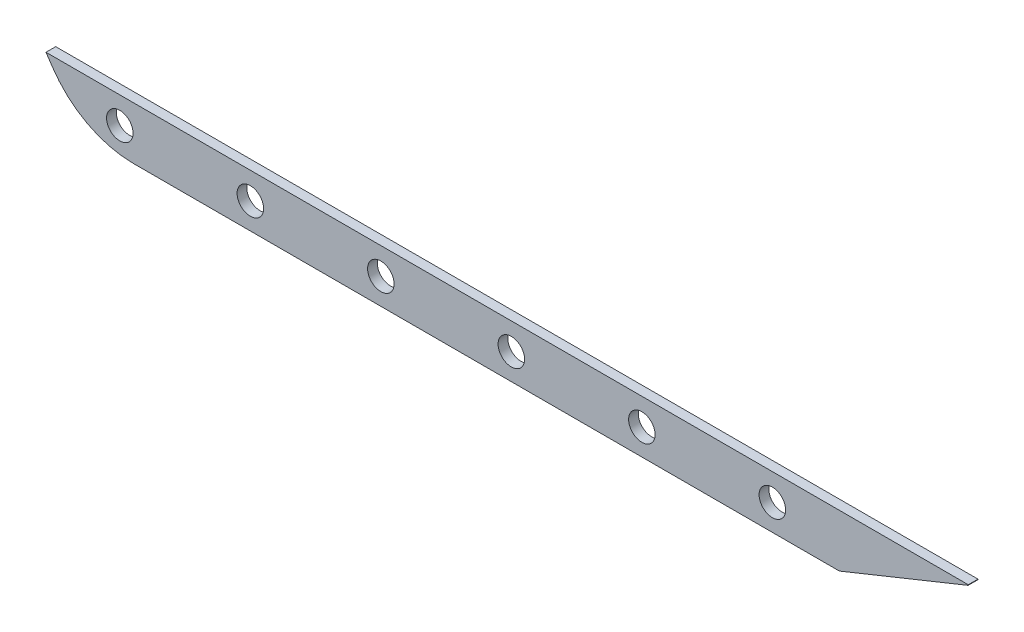
SolidWorks part; units mm, degrees
material "5052-H34"
ref_plane "Front Plane" through (0, 0, 0) normal (0, 0, 1) x (1, 0, 0)
ref_plane "Top Plane" through (0, 0, 0) normal (0, 1, 0) x (1, 0, 0)
ref_plane "Right Plane" through (0, 0, 0) normal (1, 0, 0) x (0, 0, -1)
sketch "Sketch1" plane through (0, 0, 0) normal (0, 0, 1) x (1, 0, 0)
  line L3 (428.1206, 28.9396) -> (0.5404, 28.9396)
  line L6 (-98.8794, 3.851) -> (-31.8794, -96.649)
  line L7 (428.1206, 28.9396) -> (403.1206, -71.149)
  line L9 (403.1206, -71.149) -> (366, -96.649)
  line L10 (-31.8794, -96.649) -> (366, -96.649)
  line L11 (0.5404, 28.9396) -> (-115.6052, 28.9396)
  line L12 (-98.8794, 3.851) -> (-115.6052, 28.9396)
  line L13 (-49.0861, -70.839) -> (403.198, -70.839)
  circle A0 centre (-12.8794, -83.899) radius 6.5
  circle A1 centre (51.1206, -83.899) radius 6.5
  circle A2 centre (115.1206, -83.899) radius 6.5
  circle A3 centre (179.1206, -83.899) radius 6.5
  circle A4 centre (243.1206, -83.899) radius 6.5
  circle A5 centre (307.1206, -83.899) radius 6.5
  point P0 (-48.8794, -71.149)
  point P2 (-31.8794, -96.649)
  point P8 (48, -83.899)
  point P9 (403.1206, -71.149)
  point P23 (-49.0861, -70.839)
  point P26 (403.198, -70.839)
  dimension "D2" = 64
  dimension "D4" = 64
  dimension "D1" = 25.5
  dimension "D3" = 75
  dimension "D5" = 25
  dimension "D6" = 96
  dimension "D7" = 527
  dimension "D8" = 180
  dimension "D9" = 64
  dimension "D10" = 64
  dimension "D11" = 64
  dimension "D12" = 123.69
  dimension "D13" = 12.75
  dimension "D14" = 25.81
  dimension "D15" = 25.81
extrude "Boss-Extrude1" add sketch "Sketch1" along normal blind 4.7625 contours L3 L11 L12 L6 L10 L9 L7
extrude "Cut-Extrude1" cut sketch "Sketch1<4>" along normal through all contours A0 | A1 | A2 | A3 | A4 | A5 region at (-12.8794, -83.899, 0)
sketch "Sketch1<4>" plane through (0, 0, 0) normal (0, 0, 1) x (1, 0, 0) same geometry as "Sketch1"
sketch "Sketch2" plane through (0, 0, 0) normal (0, 0, -1) x (-1, 0, 0)
  circle A0 centre (-275.1206, -83.899) radius 6.5
  circle A2 centre (-233.5603, -132.5687) radius 6.5
  circle A3 centre (-192, -83.899) radius 6.5
  circle A4 centre (-128, -83.899) radius 6.5
  circle A5 centre (-64, -83.899) radius 6.5
  circle A6 centre (0, -83.899) radius 6.5
  dimension "D2" = 0
  dimension "D3" = 64
  dimension "D4" = 64
  dimension "D5" = 64
  dimension "D6" = 64
  dimension "D7" = 64
  dimension "D1" = 32
sketch "Sketch5" plane through (0, 0, 0) normal (0, 0, -1) x (-1, 0, 0)
  line L0 (48.8794, -71.149) -> (-14.2353, -96.649)
  line L1 (31.8794, -96.649) -> (-366, -96.649) construction
  line L2 (-14.2353, -96.649) -> (31.8794, -96.649)
  line L3 (31.8794, -96.649) -> (48.8794, -71.149)
  line L6 (-366, -96.649) -> (-403.1206, -71.149)
  line L7 (-403.1206, -71.149) -> (-352, -71.149)
  line L9 (-352, -71.149) -> (-326.5, -96.649)
  line L11 (-366, -96.649) -> (-326.5, -96.649)
  dimension "D1" = 22
  dimension "D2" = 45
extrude "Cut-Extrude2" [suppressed] cut sketch "Sketch5" against normal up to next
sketch "Sketch6" plane through (0, 0, 4.7625) normal (0, 0, 1) x (1, 0, 0)
  line L0 (-48.8794, -71.149) -> (14.2353, -96.649)
  line L1 (-31.8794, -96.649) -> (366, -96.649) construction
  line L2 (14.2353, -96.649) -> (-31.8794, -96.649)
  line L3 (-31.8794, -96.649) -> (-48.8794, -71.149)
  dimension "D1" = 158
fillet "Fillet1" radius 48 1 edges at (-31.8794, -96.649, 2.3813)
sketch "Sketch7" plane through (0, 0, 4.7625) normal (0, 0, 1) x (1, 0, 0)
  line L0 (403.1206, -71.149) -> (340.0059, -96.649)
  line L1 (-31.8794, -96.649) -> (366, -96.649) construction
  line L2 (340.0059, -96.649) -> (366, -96.649)
  line L3 (366, -96.649) -> (403.1206, -71.149)
  dimension "D1" = 22
extrude "Cut-Extrude3" cut sketch "Sketch7" against normal blind 10
sketch "Sketch9" plane through (0, 0, 0) normal (0, 0, -1) x (-1, 0, 0)
  line L0 (-403.1206, -71.149) -> (48.8794, -71.149)
  line L1 (48.8794, -71.149) -> (48.8794, -114.9143)
  line L2 (48.8794, -114.9143) -> (-403.1206, -114.9143)
  line L3 (-403.1206, -114.9143) -> (-403.1206, -71.149)
extrude "Cut-Extrude4" [suppressed] cut sketch "Sketch9" against normal blind 10
sketch "Sketch10" plane through (0, 0, 4.7625) normal (0, 0, 1) x (1, 0, 0)
  line L0 (-49.0861, -70.839) -> (403.198, -70.839) construction
  line L1 (-49.0861, -70.839) -> (403.198, -70.839)
  line L2 (-49.0861, -70.839) -> (-115.6052, 28.9396)
  line L3 (-115.6052, 28.9396) -> (428.1206, 28.9396)
  line L4 (428.1206, 28.9396) -> (403.198, -70.839)
extrude "Cut-Extrude5" cut sketch "Sketch10" against normal blind 10
